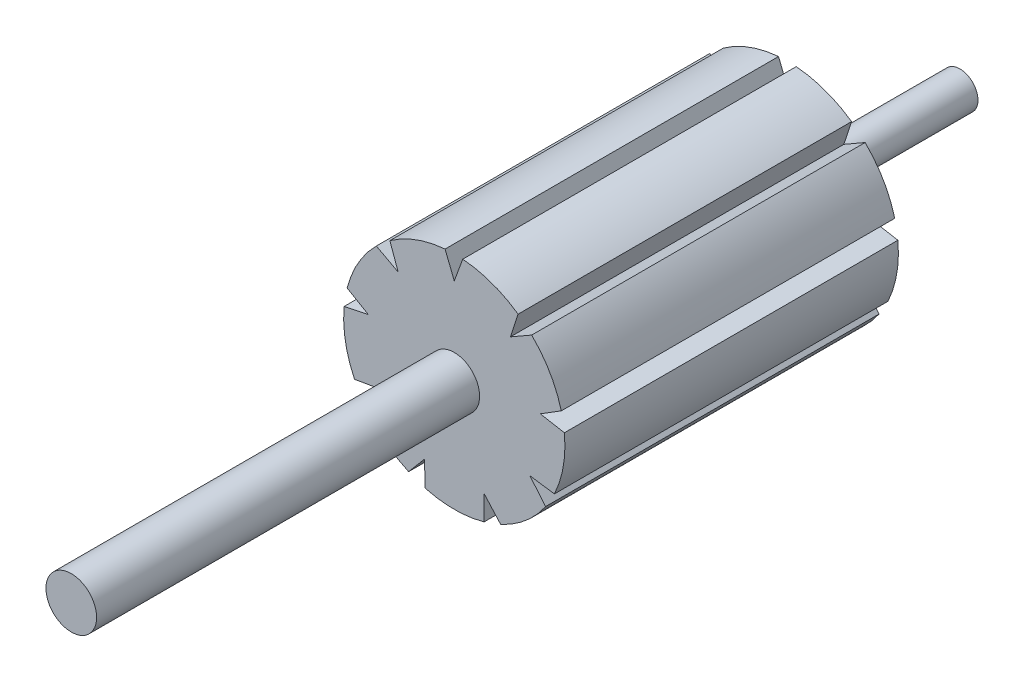
SolidWorks part; units mm, degrees
material "Ductile Iron"
ref_plane "Front Plane" through (0, 0, 0) normal (0, 0, 1) x (1, 0, 0)
ref_plane "Top Plane" through (0, 0, 0) normal (0, 1, 0) x (1, 0, 0)
ref_plane "Right Plane" through (0, 0, 0) normal (1, 0, 0) x (0, 0, -1)
sketch "Sketch1" plane through (0, 0, 0) normal (0, 0, 1) x (1, 0, 0)
  line L0 (3.1026, 3.6976) -> (4.2796, 4.3732)
  line L1 (0, 4.8268) -> (0.4673, 6.101)
  line L3 (-0.51, 6.0975) -> (0, 4.8268)
  line L4 (3.5287, 4.9988) -> (3.1026, 3.6976)
  line L5 (4.7535, 0.8382) -> (6.0894, 0.5992)
  line L6 (5.9163, 1.5611) -> (4.7535, 0.8382)
  line L7 (4.1802, -2.4134) -> (5.0499, -3.4552)
  line L8 (5.5356, -2.6071) -> (4.1802, -2.4134)
  line L9 (1.6509, -4.5358) -> (1.6475, -5.8929)
  line L10 (2.5647, -5.5554) -> (1.6509, -4.5358)
  line L11 (-1.6509, -4.5358) -> (-2.5258, -5.5732)
  line L12 (-1.6062, -5.9042) -> (-1.6509, -4.5358)
  line L13 (-4.1802, -2.4134) -> (-5.5173, -2.6458)
  line L14 (-5.0256, -3.4904) -> (-4.1802, -2.4134)
  line L15 (-4.7535, 0.8382) -> (-5.9271, 1.5197)
  line L16 (-6.0935, 0.5566) -> (-4.7535, 0.8382)
  line L17 (-3.1026, 3.6976) -> (-3.5636, 4.974)
  line L18 (-4.3101, 4.3432) -> (-3.1026, 3.6976)
  arc A1 (-0.51, 6.0975) -> (-3.5636, 4.974) centre (0, 0) ccw
  arc A2 (3.5287, 4.9988) -> (0.4673, 6.101) centre (0, 0) ccw
  arc A3 (5.9163, 1.5611) -> (4.2796, 4.3732) centre (0, 0) ccw
  arc A4 (5.5356, -2.6071) -> (6.0894, 0.5992) centre (0, 0) ccw
  arc A5 (2.5647, -5.5554) -> (5.0499, -3.4552) centre (0, 0) ccw
  arc A6 (-1.6062, -5.9042) -> (1.6475, -5.8929) centre (0, 0) ccw
  arc A7 (-5.0256, -3.4904) -> (-2.5258, -5.5732) centre (0, 0) ccw
  arc A8 (-6.0935, 0.5566) -> (-5.5173, -2.6458) centre (0, 0) ccw
  arc A9 (-4.3101, 4.3432) -> (-5.9271, 1.5197) centre (0, 0) ccw
  point P32 (0, 0)
  dimension "D1" = 12.2377
  dimension "D2" = 9
extrude "Boss-Extrude1" add sketch "Sketch1" along normal blind 18.44
sketch "Sketch2" plane through (0, 0, 18.44) normal (0, 0, 1) x (1, 0, 0)
  circle A0 centre (0, 0) radius 1.4003
sketch "Sketch7" plane through (0, 0, 0) normal (0, 0, -1) x (-1, 0, 0)
  line L0 (0, 4.8268) -> (0, -6.0188) construction
  circle A1 centre (0, 0) radius 1
extrude "Boss-Extrude4" add sketch "Sketch7" along normal blind 9.52
extrude "Boss-Extrude5" add sketch "Sketch2" along normal blind 21.18
